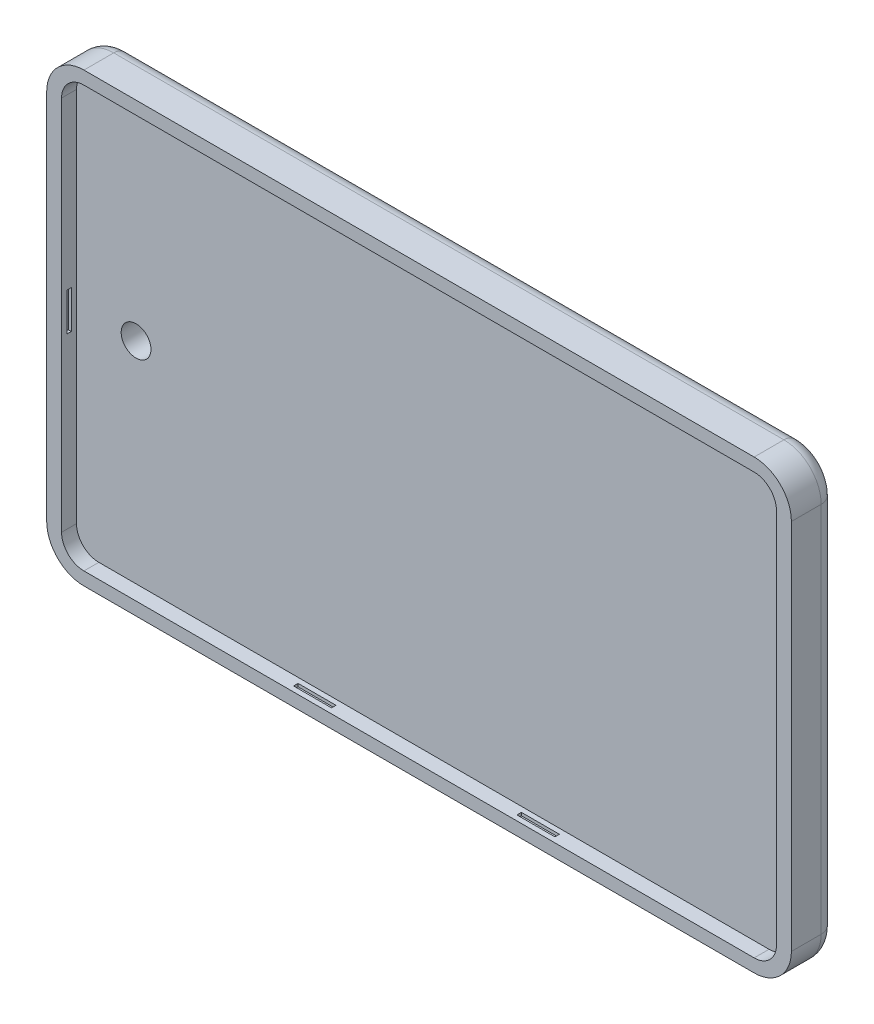
SolidWorks part; units mm, degrees
ref_plane "前视基准面" through (0, 0, 0) normal (0, 0, 1) x (1, 0, 0)
ref_plane "上视基准面" through (0, 0, 0) normal (0, 1, 0) x (1, 0, 0)
ref_plane "右视基准面" through (0, 0, 0) normal (1, 0, 0) x (0, 0, -1)
other "Configuration Table"
sketch "草图1" plane through (0, 0, 0) normal (0, 0, 1) x (1, 0, 0)
  line L1 (50, 30) -> (-50, 30)
  line L2 (50, 30) -> (50, -30)
  line L3 (50, -30) -> (-50, -30)
  line L4 (-50, 30) -> (-50, -30)
  line L5 (50, 30) -> (-50, -30) construction
  line L6 (50, -30) -> (-50, 30) construction
  point P0 (0, 0)
  dimension "D1" = 100
  dimension "D2" = 60
extrude "凸台-拉伸1" add sketch "草图1" along normal blind 6
fillet "圆角1" radius 5 4 edges at (-50, -30, 3) (50, -30, 3) (50, 30, 3) (-50, 30, 3)
fillet "圆角2" radius 2 8 edges at (48.5355, -28.5355, 0) (50, 0, 0) (48.5355, 28.5355, 0) (0, 30, 0) (-48.5355, 28.5355, 0) (-50, 0, 0) (-48.5355, -28.5355, 0) (0, -30, 0)
sketch "草图2" plane through (0, 0, 6) normal (0, 0, 1) x (1, 0, 0)
  line L1 (-45, 28.25) -> (45, 28.25)
  line L2 (-48, 25.25) -> (-48, -25.25)
  line L3 (-45, -28.25) -> (45, -28.25)
  line L4 (48, 25.25) -> (48, -25.25)
  line L5 (-48, 28.25) -> (48, -28.25) construction
  line L6 (-48, -28.25) -> (48, 28.25) construction
  arc A0 (45, -28.25) -> (48, -25.25) centre (45, -25.25) ccw
  arc A1 (48, 25.25) -> (45, 28.25) centre (45, 25.25) ccw
  arc A2 (-45, 28.25) -> (-48, 25.25) centre (-45, 25.25) ccw
  arc A3 (-45, -28.25) -> (-48, -25.25) centre (-45, -25.25) cw
  point P0 (0, 0)
  dimension "D1" = 3
  dimension "D2" = 96
  dimension "D3" = 56.5
extrude "切除-拉伸1" cut sketch "草图2" against normal blind 2
sketch "草图4" plane through (0, -28.25, 0) normal (0, 1, 0) x (1, 0, 0)
  line L0 (45, -5) -> (-45, -5) construction
  line L1 (17.55, -5.3) -> (12.45, -5.3)
  line L2 (17.55, -5.3) -> (17.55, -4.7)
  line L3 (17.55, -4.7) -> (12.45, -4.7)
  line L4 (12.45, -5.3) -> (12.45, -4.7)
  line L5 (17.55, -5.3) -> (12.45, -4.7) construction
  line L6 (17.55, -4.7) -> (12.45, -5.3) construction
  line L10 (-12.45, -5.3) -> (-17.55, -5.3)
  line L11 (-12.45, -5.3) -> (-12.45, -4.7)
  line L12 (-12.45, -4.7) -> (-17.55, -4.7)
  line L13 (-17.55, -5.3) -> (-17.55, -4.7)
  line L14 (-12.45, -5.3) -> (-17.55, -4.7) construction
  line L15 (-12.45, -4.7) -> (-17.55, -5.3) construction
  line L16 (45, -6) -> (45, -2) construction
  line L17 (-45, -2) -> (-45, -6) construction
  line L18 (45, -6) -> (-45, -6) construction
  point P0 (15, -5)
  point P12 (-15, -5)
  dimension "D1" = 1
  dimension "D2" = 0.6
  dimension "D3" = 5.1
  dimension "D4" = 0.6
  dimension "D5" = 5.1
  dimension "D6" = 30
  dimension "D7" = 60
extrude "切除-拉伸2" cut sketch "草图4" against normal blind 0.4
sketch "草图5" plane through (0, 28.25, 0) normal (0, -1, 0) x (1, 0, 0)
  line L0 (-17.55, 5.3) -> (-17.55, 4.7) construction
  line L1 (-12.45, 5.3) -> (-17.55, 5.3) construction
  line L2 (-12.45, 4.7) -> (-17.55, 4.7) construction
  line L3 (-12.45, 5.3) -> (-12.45, 4.7) construction
  line L4 (12.45, 5.3) -> (12.45, 4.7) construction
  line L5 (17.55, 5.3) -> (12.45, 5.3) construction
  line L6 (17.55, 5.3) -> (17.55, 4.7) construction
  line L7 (17.55, 4.7) -> (12.45, 4.7) construction
  line L8 (-17.55, 5.3) -> (-17.55, 4.7)
  line L9 (-12.45, 5.3) -> (-17.55, 5.3)
  line L10 (-12.45, 4.7) -> (-17.55, 4.7)
  line L11 (-12.45, 5.3) -> (-12.45, 4.7)
  line L12 (12.45, 5.3) -> (12.45, 4.7)
  line L13 (17.55, 5.3) -> (12.45, 5.3)
  line L14 (17.55, 5.3) -> (17.55, 4.7)
  line L15 (17.55, 4.7) -> (12.45, 4.7)
extrude "切除-拉伸3" cut sketch "草图5" against normal blind 0.4
sketch "草图6" plane through (-48, 0, 0) normal (1, 0, 0) x (0, 0, -1)
  line L0 (-6, -25) -> (-2, -25) construction
  line L1 (-5, -25) -> (-5, 25) construction
  line L2 (-2, 25) -> (-6, 25) construction
  line L3 (-6, -25) -> (-6, 25) construction
  line L5 (-5.3, -2.55) -> (-4.7, -2.55)
  line L6 (-5.3, -2.55) -> (-5.3, 2.55)
  line L7 (-5.3, 2.55) -> (-4.7, 2.55)
  line L8 (-4.7, -2.55) -> (-4.7, 2.55)
  line L9 (-5.3, -2.55) -> (-4.7, 2.55) construction
  line L10 (-5.3, 2.55) -> (-4.7, -2.55) construction
  point P8 (-5, 0)
  point P15 (-5, 0)
  dimension "D1" = 1
  dimension "D2" = 5.1
  dimension "D3" = 0.6
extrude "切除-拉伸4" cut sketch "草图6" against normal blind 0.4
sketch "草图7" plane through (48, 0, 0) normal (-1, 0, 0) x (0, 0, 1)
  line L0 (5.3, 2.55) -> (4.7, 2.55) construction
  line L1 (5.3, -2.55) -> (4.7, -2.55) construction
  line L2 (5.3, -2.55) -> (5.3, 2.55) construction
  line L3 (4.7, -2.55) -> (4.7, 2.55) construction
  line L4 (5.3, 2.55) -> (4.7, 2.55)
  line L5 (5.3, -2.55) -> (4.7, -2.55)
  line L6 (5.3, -2.55) -> (5.3, 2.55)
  line L7 (4.7, -2.55) -> (4.7, 2.55)
extrude "切除-拉伸5" cut sketch "草图7" against normal blind 0.4
sketch "草图8" plane through (0, 0, 4) normal (0, 0, 1) x (1, 0, 0)
  line L0 (0, 0) -> (-48, 0) construction
  line L1 (-48, 25.25) -> (-48, -25.25) construction
  circle A0 centre (-40, 0) radius 2
  dimension "D1" = 40
  dimension "D2" = 4
extrude "切除-拉伸6" cut sketch "草图8" against normal up to next
